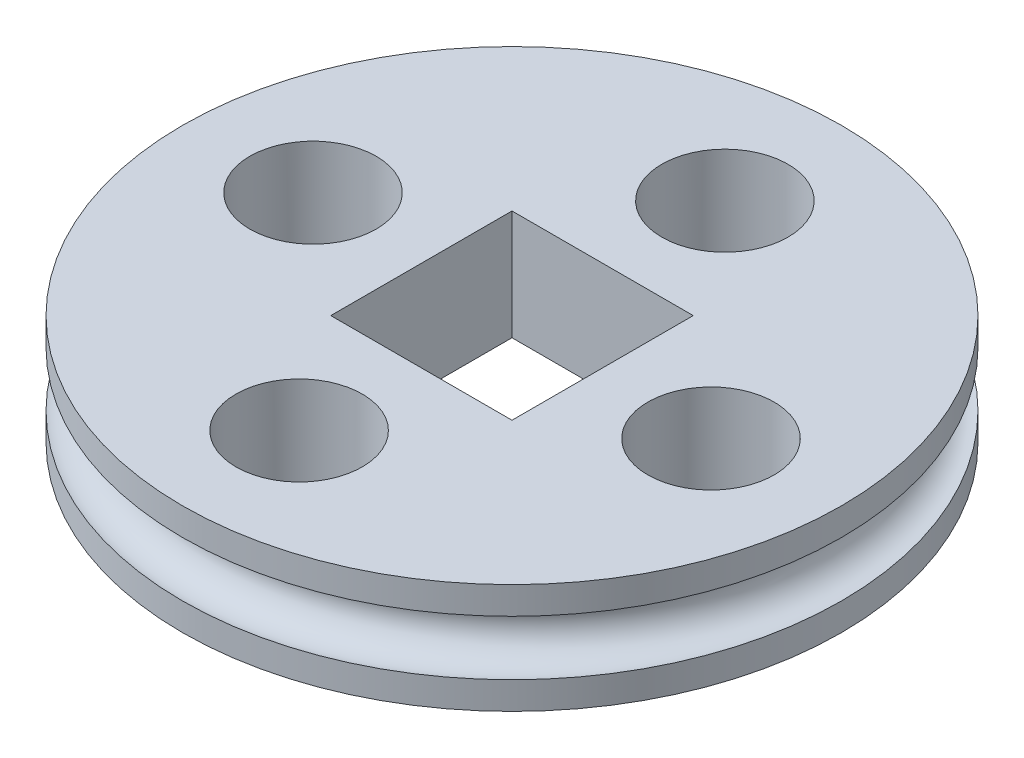
SolidWorks part; units mm, degrees
ref_plane "Ebene vorne" through (0, 0, 0) normal (0, 0, 1) x (1, 0, 0)
ref_plane "Ebene oben" through (0, 0, 0) normal (0, 1, 0) x (1, 0, 0)
ref_plane "Ebene rechts" through (0, 0, 0) normal (1, 0, 0) x (0, 0, -1)
sketch "Skizze1" plane through (0, 0, 0) normal (0, 1, 0) x (1, 0, 0)
  circle A0 centre (0, 0) radius 6
  dimension "D1" = 12
extrude "Aufsatz-Linear austragen1" add sketch "Skizze1" along normal blind 2
sketch "Skizze3" plane through (0, 2, 0) normal (0, 1, 0) x (1, 0, 0)
  line L0 (1.65, 1.65) -> (-1.65, 1.65)
  line L1 (1.65, 1.65) -> (1.65, -1.65)
  line L2 (1.65, -1.65) -> (-1.65, -1.65)
  line L3 (-1.65, 1.65) -> (-1.65, -1.65)
  line L4 (0, 0) -> (0, -3.3) construction
  line L5 (0, 0) -> (-10.1495, 0) construction
  point P8 (-1.65, 0)
  point P9 (0, -1.65)
  point P10 (0, 0)
  point P11 (0, 0)
  dimension "D1" = 1.65
  dimension "D2" = 1.65
extrude "Schnitt-Linear austragen1" cut sketch "Skizze3" against normal blind 3
sketch "Skizze4" plane through (0, 2, 0) normal (0, 1, 0) x (1, 0, 0)
  line L0 (1.65, -1.65) -> (1.65, 1.65) construction
  circle A0 centre (3.75, -0.1264) radius 1.15
  dimension "D1" = 2.3
  dimension "D2" = 2.1
extrude "Schnitt-Linear austragen2" cut sketch "Skizze4" against normal blind 3
pattern_circular "Kreismuster1" count 4 over 360 about axis through (0, 2, 0) along (0, -1, 0) of "Schnitt-Linear austragen2"
sketch "Skizze6" plane through (0, 0, 0) normal (0, 0, 1) x (1, 0, 0)
  line L5 (-6, 2) -> (-6, 0) construction
  line L6 (-6, 1.5) -> (-6, 0.5)
  arc A0 (-6, 1.5) -> (-6, 0.5) centre (-5.8956, 1) cw
revolve "Schnitt-Rotation2" cut sketch "Skizze6" angle 360 about axis through (0, 2, 0) along (0, -1, 0)
